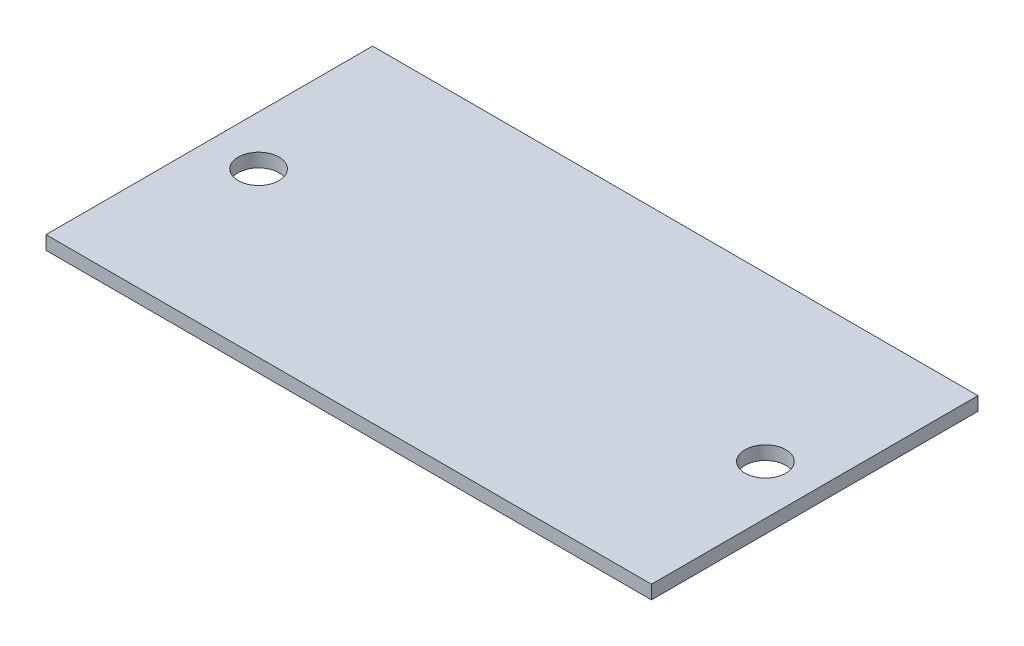
SolidWorks part; units mm, degrees
ref_plane "Front Plane" through (0, 0, 0) normal (0, 0, 1) x (1, 0, 0)
ref_plane "Top Plane" through (0, 0, 0) normal (0, 1, 0) x (1, 0, 0)
ref_plane "Right Plane" through (0, 0, 0) normal (1, 0, 0) x (0, 0, -1)
sketch "Sketch1" plane through (0, 0, 0) normal (0, 1, 0) x (1, 0, 0)
  line L0 (0, -12) -> (0, 12) construction
  line L1 (-22.25, -12) -> (22.25, -12)
  line L2 (-22.25, -12) -> (-22.25, 12)
  line L3 (-22.25, 12) -> (22.25, 12)
  line L4 (22.25, -12) -> (22.25, 12)
  line L5 (-22.25, -12) -> (22.25, 12) construction
  line L6 (-22.25, 12) -> (22.25, -12) construction
  line L7 (15, -12) -> (15, 12) construction
  line L8 (15, -12) -> (22.25, 12) construction
  circle A0 centre (18.625, 0) radius 1.5
  circle A1 centre (-18.625, 0) radius 1.5
  point P0 (0, 0)
  point P9 (0, 0)
  point P12 (15, 0)
  dimension "D4" = 3
  dimension "D1" = 44.5
  dimension "D2" = 24
  dimension "D3" = 7.25
extrude "Boss-Extrude1" add sketch "Sketch1" along normal blind 1
